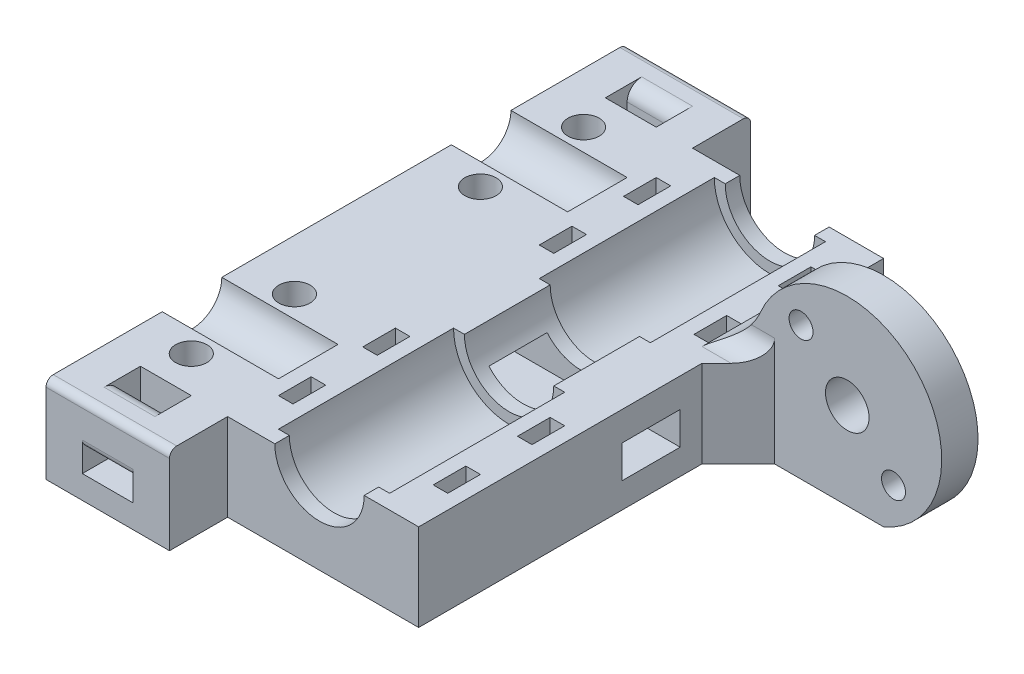
SolidWorks part; units mm, degrees
ref_plane "Alzado" through (0, 0, 0) normal (0, 0, 1) x (1, 0, 0)
ref_plane "Planta" through (0, 0, 0) normal (0, 1, 0) x (1, 0, 0)
ref_plane "Vista lateral" through (0, 0, 0) normal (1, 0, 0) x (0, 0, -1)
sketch "Croquis1" plane through (0, 0, 0) normal (0, 0, 1) x (1, 0, 0)
  line L6 (-7.65, 0) -> (-13.65, 0)
  line L7 (-13.65, 0) -> (-13.65, -12)
  line L8 (-13.65, -12) -> (11.65, -12)
  line L9 (11.65, -12) -> (11.65, 0)
  line L10 (11.65, 0) -> (7.65, 0)
  arc A2 (-7.65, 0) -> (7.65, 0) centre (0, 0) ccw
  dimension "D1" = 7.65
  dimension "D2" = 4
  dimension "D3" = 12
  dimension "D4" = 6
extrude "Saliente-Extruir1" add sketch "Croquis1" along normal blind 64
sketch "Croquis2" plane through (0, 0, 64) normal (0, 0, 1) x (1, 0, 0)
  line L0 (-7.65, 0) -> (-6.15, 0)
  line L1 (6.15, 0) -> (7.65, 0)
  arc A0 (-7.65, 0) -> (7.65, 0) centre (0, 0) ccw construction
  arc A1 (-7.65, 0) -> (7.65, 0) centre (0, 0) ccw
  arc A2 (-6.15, 0) -> (6.15, 0) centre (0, 0) ccw
  dimension "D1" = 1.5
extrude "Saliente-Extruir2" add sketch "Croquis2" against normal blind 2
sketch "Croquis3" plane through (0, 0, 0) normal (0, 0, -1) x (-1, 0, 0)
  line L2 (7.65, 0) -> (6.15, 0)
  line L3 (-6.15, 0) -> (-7.65, 0)
  line L4 (7.65, 0) -> (6.15, 0)
  line L5 (-6.15, 0) -> (-7.65, 0)
  arc A2 (-7.65, 0) -> (7.65, 0) centre (0, 0) ccw
  arc A3 (-6.15, 0) -> (6.15, 0) centre (0, 0) ccw
  arc A4 (-7.65, 0) -> (7.65, 0) centre (0, 0) ccw
  arc A5 (-6.15, 0) -> (6.15, 0) centre (0, 0) ccw
  dimension "D1" = 0
extrude "Saliente-Extruir3" add sketch "Croquis3" against normal blind 2
sketch "Croquis4" plane through (0, 0, 2) normal (0, 0, 1) x (1, 0, 0)
  line L2 (7.65, 0) -> (6.15, 0)
  line L3 (-6.15, 0) -> (-7.65, 0)
  line L4 (7.65, 0) -> (6.15, 0)
  line L5 (-6.15, 0) -> (-7.65, 0)
  arc A2 (-7.65, 0) -> (7.65, 0) centre (0, 0) ccw
  arc A3 (-6.15, 0) -> (6.15, 0) centre (0, 0) ccw
  arc A4 (-7.65, 0) -> (7.65, 0) centre (0, 0) ccw
  arc A5 (-6.15, 0) -> (6.15, 0) centre (0, 0) ccw
  dimension "D1" = 0
extrude "Saliente-Extruir4" add sketch "Croquis4" along normal blind 11.8 from offset 24.1
sketch "Croquis5" plane through (-13.65, 0, 0) normal (-1, 0, 0) x (0, 0, 1)
  line L0 (64, 0) -> (0, 0) construction
  line L1 (8, 0) -> (0, 0)
  line L2 (47.8, 0) -> (16.2, 0)
  line L4 (0, 0) -> (0, -12)
  line L5 (0, -12) -> (64, -12)
  line L6 (64, -12) -> (64, 0)
  line L7 (64, 0) -> (0, 0)
  line L8 (0, 0) -> (0, -12)
  line L9 (0, -12) -> (64, -12)
  line L10 (64, -12) -> (64, 0)
  line L11 (64, 0) -> (56, 0)
  arc A0 (8, 0) -> (16.2, 0) centre (12.1, 0) ccw
  arc A1 (56, 0) -> (47.8, 0) centre (51.9, 0) cw
  dimension "D3" = 4.1
  dimension "D2" = 8
  dimension "D4" = 8
  dimension "D1" = 0
extrude "Saliente-Extruir5" add sketch "Croquis5" along normal blind 16
sketch "Croquis6" plane through (0, 0, 0) normal (0, 1, 0) x (1, 0, 0)
  line L0 (-29.65, -8) -> (-29.65, 0) construction
  line L3 (-22.65, -19.2) -> (-22.65, -5) construction
  line L4 (-22.65, -59) -> (-22.65, -44.8) construction
  line L5 (-13.65, -56) -> (-13.65, -47.8) construction
  line L6 (-29.65, -8) -> (-29.65, -16.2) construction
  circle A0 centre (-22.65, -59) radius 2.15
  circle A1 centre (-22.65, -5) radius 2.15
  circle A2 centre (-22.65, -19.2) radius 2.15
  circle A3 centre (-22.65, -44.8) radius 2.15
  point P6 (-20.65, -19.6313)
  point P7 (-22.65, -12.1)
  point P14 (-22.65, -51.9)
  point P17 (-13.65, -51.9)
  point P18 (-29.65, -12.1)
  dimension "D3" = 4.3
  dimension "D1" = 7
  dimension "D2" = 14.2
extrude "Cortar-Extruir1" cut sketch "Croquis6" against normal through all
sketch "Croquis7" plane through (11.65, 0, 0) normal (1, 0, 0) x (0, 0, -1)
  line L5 (-64, 0) -> (0, 0) construction
  line L6 (-36, -4) -> (-28, -4)
  line L7 (-36, -4) -> (-36, -8.5)
  line L8 (-36, -8.5) -> (-28, -8.5)
  line L9 (-28, -4) -> (-28, -8.5)
  point P4 (-32, -4)
  point P7 (-32, 0)
  dimension "D1" = 8.5
  dimension "D2" = 4
  dimension "D3" = 8
extrude "Cortar-Extruir2" cut sketch "Croquis7" against normal through all
sketch "Croquis8" plane through (0, 0, 37.9) normal (0, 0, 1) x (1, 0, 0)
  line L0 (-9.65, 0) -> (-11.65, 0)
  line L1 (-6.15, 0) -> (-29.65, 0) construction
  line L2 (7.65, 0) -> (6.15, 0)
  line L3 (-6.15, 0) -> (-7.65, 0)
  line L4 (7.65, 0) -> (6.15, 0) construction
  line L6 (-11.65, 0) -> (-11.65, -6)
  line L7 (-11.65, -6) -> (-5.65, -12)
  line L8 (-29.65, -12) -> (11.65, -12) construction
  line L9 (-5.65, -12) -> (5.65, -12)
  line L10 (5.65, -12) -> (11.65, -6)
  line L11 (11.65, -12) -> (11.65, 0) construction
  line L12 (11.65, -6) -> (11.65, 0)
  line L13 (11.65, 0) -> (9.65, 0)
  line L14 (11.65, 0) -> (6.15, 0) construction
  line L15 (9.65, 0) -> (9.65, -5.1716)
  line L16 (9.65, -5.1716) -> (4.8216, -10)
  line L17 (4.8216, -10) -> (-4.8216, -10)
  line L18 (-4.8216, -10) -> (-9.65, -5.1716)
  line L19 (-9.65, -5.1716) -> (-9.65, 0)
  line L22 (-6.15, 0) -> (-7.65, 0) construction
  arc A2 (-7.65, 0) -> (7.65, 0) centre (0, 0) ccw
  arc A3 (-6.15, 0) -> (6.15, 0) centre (0, 0) ccw
  arc A5 (-6.15, 0) -> (6.15, 0) centre (0, 0) ccw construction
  arc A6 (-7.65, 0) -> (7.65, 0) centre (0, 0) ccw construction
  point P3 (0, -12)
  point P10 (0, -10)
  point P28 (5.8099, -10)
  point P29 (0, 0)
  dimension "D2" = 2
  dimension "D3" = 2
  dimension "D4" = 2
  dimension "D5" = 45
  dimension "D6" = 6
  dimension "D1" = 0
extrude "Cortar-Extruir3" cut sketch "Croquis8" along normal blind 4.5 from offset 4
fillet "Redondeo1" radius 3 5 edges at (-11.65, -6, 44.15) (-9.65, -5.1716, 44.15) (-4.8216, -10, 44.15) (4.8216, -10, 44.15) (9.65, -5.1716, 44.15)
sketch "Croquis10" plane through (0, 0, 62) normal (0, 0, -1) x (-1, 0, 0)
  line L12 (5.65, -12) -> (10.7713, -6.8787)
  line L13 (11.65, -4.7574) -> (11.65, 0)
  line L14 (11.65, 0) -> (9.65, 0)
  line L15 (9.65, 0) -> (9.65, -3.9289)
  line L16 (8.7713, -6.0503) -> (5.7003, -9.1213)
  line L17 (3.5789, -10) -> (-3.5789, -10)
  line L18 (-5.7003, -9.1213) -> (-8.7713, -6.0503)
  line L19 (-9.65, -3.9289) -> (-9.65, 0)
  line L20 (-9.65, 0) -> (-11.65, 0)
  line L21 (-11.65, 0) -> (-11.65, -6)
  line L22 (-11.65, -6) -> (-5.65, -12)
  line L23 (-5.65, -12) -> (5.65, -12)
  line L24 (5.65, -12) -> (10.7713, -6.8787)
  line L25 (11.65, -4.7574) -> (11.65, 0)
  line L26 (11.65, 0) -> (9.65, 0)
  line L27 (9.65, 0) -> (9.65, -3.9289)
  line L28 (8.7713, -6.0503) -> (5.7003, -9.1213)
  line L29 (3.5789, -10) -> (-3.5789, -10)
  line L30 (-5.7003, -9.1213) -> (-8.7713, -6.0503)
  line L31 (-9.65, -3.9289) -> (-9.65, 0)
  line L32 (-9.65, 0) -> (-11.65, 0)
  line L33 (-11.65, 0) -> (-11.65, -6)
  line L34 (-11.65, -6) -> (-5.65, -12)
  line L35 (-5.65, -12) -> (5.65, -12)
  arc A5 (10.7713, -6.8787) -> (11.65, -4.7574) centre (8.65, -4.7574) ccw
  arc A6 (8.7713, -6.0503) -> (9.65, -3.9289) centre (6.65, -3.9289) ccw
  arc A7 (3.5789, -10) -> (5.7003, -9.1213) centre (3.5789, -7) ccw
  arc A8 (-5.7003, -9.1213) -> (-3.5789, -10) centre (-3.5789, -7) ccw
  arc A9 (-9.65, -3.9289) -> (-8.7713, -6.0503) centre (-6.65, -3.9289) ccw
  arc A10 (10.7713, -6.8787) -> (11.65, -4.7574) centre (8.65, -4.7574) ccw
  arc A11 (8.7713, -6.0503) -> (9.65, -3.9289) centre (6.65, -3.9289) ccw
  arc A12 (3.5789, -10) -> (5.7003, -9.1213) centre (3.5789, -7) ccw
  arc A13 (-5.7003, -9.1213) -> (-3.5789, -10) centre (-3.5789, -7) ccw
  arc A14 (-9.65, -3.9289) -> (-8.7713, -6.0503) centre (-6.65, -3.9289) ccw
  dimension "D1" = 0
extrude "Cortar-Extruir4" cut sketch "Croquis10" along normal blind 4.5 from offset 4
ref_plane "Plano1" through (0, 0, 32) normal (0, 0, -1) x (-1, 0, 0)
mirror "Simetría1" about plane through (0, 0, 32) normal (0, 0, -1) of "Redondeo1", "Cortar-Extruir4", "Cortar-Extruir3"
sketch "Croquis11" plane through (0, -12, 0) normal (0, -1, 0) x (1, 0, 0)
  line L1 (-18.5508, 5) -> (-20.6004, 8.55)
  line L2 (-20.6004, 8.55) -> (-24.6996, 8.55)
  line L3 (-24.6996, 8.55) -> (-26.7492, 5)
  line L4 (-26.7492, 5) -> (-24.6996, 1.45)
  line L5 (-24.6996, 1.45) -> (-20.6004, 1.45)
  line L6 (-20.6004, 1.45) -> (-18.5508, 5)
  line L7 (-18.5508, 19.2) -> (-20.6004, 22.75)
  line L8 (-20.6004, 22.75) -> (-24.6996, 22.75)
  line L9 (-24.6996, 22.75) -> (-26.7492, 19.2)
  line L10 (-26.7492, 19.2) -> (-24.6996, 15.65)
  line L11 (-24.6996, 15.65) -> (-20.6004, 15.65)
  line L12 (-20.6004, 15.65) -> (-18.5508, 19.2)
  line L13 (-18.5508, 44.8) -> (-20.6004, 48.35)
  line L14 (-20.6004, 48.35) -> (-24.6996, 48.35)
  line L15 (-24.6996, 48.35) -> (-26.7492, 44.8)
  line L16 (-26.7492, 44.8) -> (-24.6996, 41.25)
  line L17 (-24.6996, 41.25) -> (-20.6004, 41.25)
  line L18 (-20.6004, 41.25) -> (-18.5508, 44.8)
  line L19 (-18.5508, 59) -> (-20.6004, 62.55)
  line L20 (-20.6004, 62.55) -> (-24.6996, 62.55)
  line L21 (-24.6996, 62.55) -> (-26.7492, 59)
  line L22 (-26.7492, 59) -> (-24.6996, 55.45)
  line L23 (-24.6996, 55.45) -> (-20.6004, 55.45)
  line L24 (-20.6004, 55.45) -> (-18.5508, 59)
  circle A0 centre (-22.65, 5) radius 3.55 construction
  circle A1 centre (-22.65, 19.2) radius 3.55 construction
  circle A2 centre (-22.65, 44.8) radius 3.55 construction
  circle A3 centre (-22.65, 59) radius 3.55 construction
  dimension "D1" = 7.1
extrude "Cortar-Extruir5" cut sketch "Croquis11" against normal blind 4
sketch "Croquis13" plane through (0, 0, 0) normal (0, 1, 0) x (1, 0, 0)
  line L1 (-29.65, -64) -> (-12.65, -64)
  line L2 (-29.65, -64) -> (-29.65, -72)
  line L3 (-29.65, -72) -> (-12.65, -72)
  line L4 (-12.65, -64) -> (-12.65, -72)
  dimension "D1" = 8
  dimension "D2" = 17
extrude "Saliente-Extruir6" add sketch "Croquis13" against normal up to surface (12 mm away) up to face at (-22.65, -12, 5)
sketch "Croquis14" plane through (-12.65, 0, 0) normal (1, 0, 0) x (0, 0, -1)
  line L0 (-72, -5.8) -> (-67, -5.8)
  line L1 (-72, -12) -> (-72, 0) construction
  line L2 (-67, -5.8) -> (-67, 0)
  line L3 (-72, 0) -> (-64, 0) construction
  line L4 (-67, 0) -> (-64, 0)
  line L5 (-64, 0) -> (-64, -8.8)
  line L6 (-64, -12) -> (-64, 0) construction
  line L7 (-64, -8.8) -> (-72, -8.8)
  line L8 (-72, -8.8) -> (-72, -5.8)
  dimension "D1" = 3
  dimension "D2" = 5.8
  dimension "D3" = 3
extrude "Cortar-Extruir6" cut sketch "Croquis14" against normal blind 7 from offset 5 offset against normal yes
fillet "Redondeo2" radius 2 3 edges at (-21.15, -5.8, 67) (-21.15, 0, 67) (-21.15, -8.8, 64)
fillet "Redondeo3" radius 1 2 edges at (-21.15, 0, 72) (-21.15, -5.8, 72)
mirror "Simetría2" about plane through (0, 0, 32) normal (0, 0, -1) of "Redondeo3", "Redondeo2", "Cortar-Extruir6", "Saliente-Extruir6"
sketch "Croquis15" plane through (11.65, 0, 0) normal (1, 0, 0) x (0, 0, -1)
  line L0 (-28, -4) -> (-36, -4) construction
  line L1 (0, 0) -> (-64, 0)
  line L2 (0, 0) -> (0, -12)
  line L3 (0, -12) -> (-64, -12)
  line L4 (-64, 0) -> (-64, -12)
  line L5 (-28, -8.5) -> (-28, -4) construction
  line L6 (-36, -8.5) -> (-28, -8.5) construction
  line L7 (-36, -4) -> (-36, -8.5) construction
  line L8 (-28, -4) -> (-36, -4)
  line L9 (-28, -8.5) -> (-28, -4)
  line L10 (-36, -8.5) -> (-28, -8.5)
  line L11 (-36, -4) -> (-36, -8.5)
extrude "Saliente-Extruir7" add sketch "Croquis15" along normal blind 2
sketch "Croquis16" plane through (0, 0, 28) normal (0, 0, -1) x (-1, 0, 0)
  line L3 (-13.65, -12) -> (-13.65, 0)
  line L4 (-13.65, -12) -> (-33.65, -12)
  line L5 (-13.65, 0) -> (-13.65, -12) construction
  line L7 (-15.65, 0) -> (-13.65, 0)
  arc A0 (-15.65, 0) -> (-33.65, -12) centre (-28.65, 0) ccw
  circle A2 centre (-28.65, 0) radius 3
  dimension "D1" = 13
  dimension "D6" = 6
  dimension "D2" = 15
extrude "Saliente-Extruir8" add sketch "Croquis16" along normal blind 5 from offset 8
sketch "Croquis17" plane through (0, 0, 20) normal (0, 0, 1) x (1, 0, 0)
  line L4 (13.65, 0) -> (6.15, 0) construction
  line L5 (16.7139, 5.1508) -> (16.7139, 0)
  line L6 (16.7139, 0) -> (11.65, 0)
  line L7 (13.65, -12) -> (13.65, 0) construction
  arc A2 (11.65, 0) -> (16.7139, 5.1508) centre (7.5324, 9.1129) ccw
  arc A3 (33.65, -12) -> (15.65, 0) centre (28.65, 0) ccw construction
  dimension "D2" = 2
  dimension "D1" = 10
extrude "Saliente-Extruir9" add sketch "Croquis17" against normal up to surface (5 mm away) up to face at (21.9528, -1.7958, 15)
chamfer "Chaflán1" distance 2 angle 45 1 edges at (13.65, -6, 15)
chamfer "Chaflán2" distance 5 angle 45 1 edges at (13.65, -6, 20)
fillet "Redondeo5" radius 3 1 edges at (15.15, 0, 20)
sketch "Croquis19" plane through (0, 0, 15) normal (0, 0, -1) x (-1, 0, 0)
  line L0 (-22.286, 6.364) -> (-35.014, -6.364) construction
  line L1 (-33.65, -12) -> (-15.65, -12) construction
  circle A0 centre (-28.65, 0) radius 3 construction
  circle A1 centre (-22.286, 6.364) radius 1.65
  circle A2 centre (-35.014, -6.364) radius 1.65
  point P4 (-28.65, 0)
  dimension "D3" = 3.3
  dimension "D4" = 3.3
  dimension "D1" = 45
  dimension "D2" = 18
extrude "Cortar-Extruir7" cut sketch "Croquis19" against normal through all
